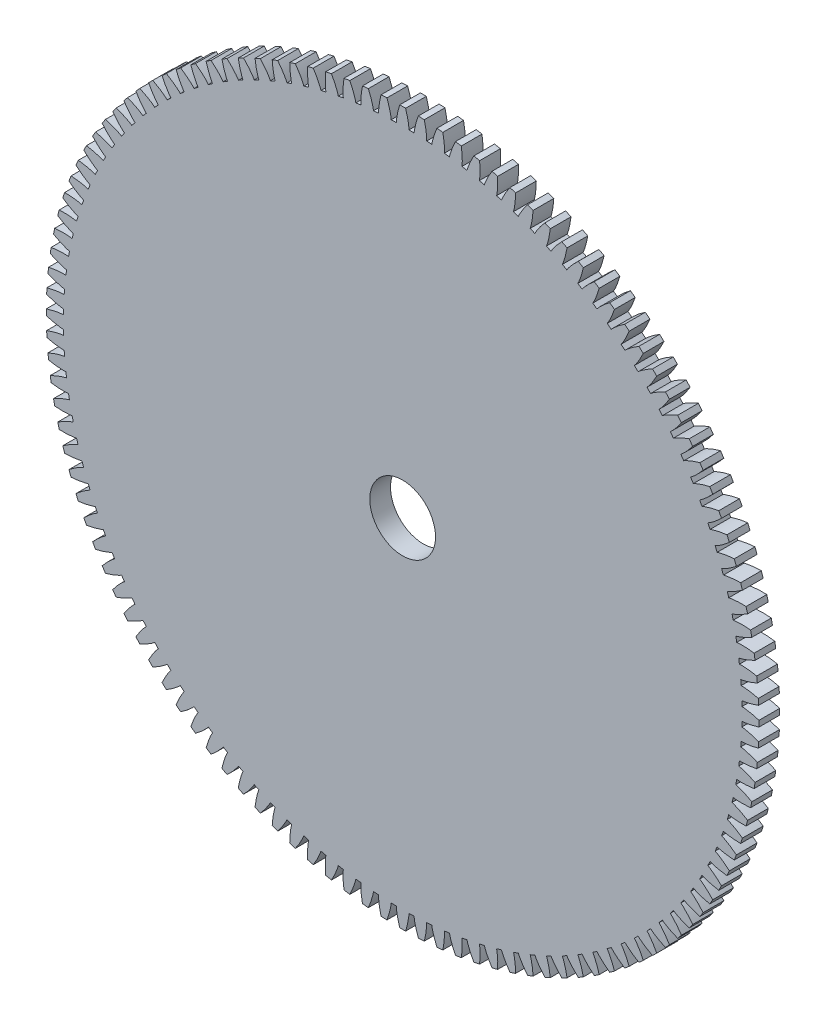
SolidWorks part; units mm, degrees
material "Brass"
ref_plane "Front Plane" through (0, 0, 0) normal (0, 0, 1) x (1, 0, 0)
ref_plane "Top Plane" through (0, 0, 0) normal (0, 1, 0) x (1, 0, 0)
ref_plane "Right Plane" through (0, 0, 0) normal (1, 0, 0) x (0, 0, -1)
sketch "Sketch1" plane through (0, 0, 0) normal (0, 0, 1) x (1, 0, 0)
  circle A0 centre (0, 0) radius 51.6467
  dimension "D1" = 103.2933
extrude "Boss-Extrude1" add sketch "Sketch1" along normal blind 3
sketch "Sketch2" plane through (0, 0, 0) normal (0, 0, 1) x (1, 0, 0)
  spline S0 degree 4 poles (49.1734, 0.9164) (49.1838, 0.9166) (49.2037, 0.9164) (49.236, 0.9157) (49.2811, 0.9138) (49.3345, 0.9109) (49.3975, 0.9065) (49.4669, 0.9007) (49.5426, 0.8933) (49.6181, 0.8849) (49.6937, 0.8757) (49.769, 0.8656) (49.8604, 0.8525) (49.9703, 0.8355) (50.099, 0.8136) (50.2454, 0.7864) (50.3952, 0.7562) (50.5429, 0.7245) (50.6927, 0.69) (50.8381, 0.655) (50.9896, 0.6161) (51.1298, 0.579) (51.2875, 0.5348) (51.415, 0.4982) (51.584, 0.4471) (51.6841, 0.416) (51.8014, 0.3786) (51.8537, 0.3614) (51.8859, 0.3509) knots 0 0 0 0 0 0.015084 0.028532 0.04661 0.064855 0.092111 0.119476 0.146842 0.174209 0.201575 0.228941 0.256307 0.307035 0.361767 0.4165 0.471232 0.525964 0.580697 0.635429 0.690161 0.744894 0.799626 0.854358 0.909091 0.954545 1 1 1 1 1 construction
  spline S1 degree 4 poles (49.1734, 0.9164) (49.1838, 0.9166) (49.2037, 0.9164) (49.236, 0.9157) (49.2811, 0.9138) (49.3345, 0.9109) (49.3975, 0.9065) (49.4669, 0.9007) (49.5426, 0.8933) (49.6181, 0.8849) (49.6937, 0.8757) (49.769, 0.8656) (49.8604, 0.8525) (49.9703, 0.8355) (50.099, 0.8136) (50.2454, 0.7864) (50.3952, 0.7562) (50.5429, 0.7245) (50.6927, 0.69) (50.8381, 0.655) (50.9896, 0.6161) (51.1298, 0.579) (51.2875, 0.5348) (51.415, 0.4982) (51.5474, 0.4582) (51.6119, 0.4383) (51.6449, 0.428) knots 0 0 0 0 0 0.015084 0.028532 0.04661 0.064855 0.092111 0.119476 0.146842 0.174209 0.201575 0.228941 0.256307 0.307035 0.361767 0.4165 0.471232 0.525964 0.580697 0.635429 0.690161 0.744894 0.799626 0.854358 0.909091 0.909091 0.909091 0.909091 0.909091
  spline S2 degree 4 poles (49.1539, 1.6583) (49.1644, 1.6588) (49.1842, 1.66) (49.2165, 1.6624) (49.2614, 1.6666) (49.3146, 1.6723) (49.3773, 1.68) (49.4463, 1.6894) (49.5214, 1.7008) (49.5965, 1.7131) (49.6714, 1.7263) (49.7461, 1.7403) (49.8367, 1.7581) (49.9455, 1.7809) (50.0729, 1.8095) (50.2177, 1.8443) (50.3657, 1.8823) (50.5116, 1.9217) (50.6594, 1.964) (50.8027, 2.0066) (50.952, 2.0533) (51.09, 2.0977) (51.2452, 2.1502) (51.3706, 2.1933) (51.5367, 2.2532) (51.635, 2.2895) (51.7503, 2.333) (51.8016, 2.3529) (51.8332, 2.3651) knots 0 0 0 0 0 0.015084 0.028532 0.04661 0.064855 0.092111 0.119476 0.146842 0.174209 0.201575 0.228941 0.256307 0.307035 0.361767 0.4165 0.471232 0.525964 0.580697 0.635429 0.690161 0.744894 0.799626 0.854358 0.909091 0.954545 1 1 1 1 1 construction
  spline S3 degree 4 poles (49.1539, 1.6583) (49.1644, 1.6588) (49.1842, 1.66) (49.2165, 1.6624) (49.2614, 1.6666) (49.3146, 1.6723) (49.3773, 1.68) (49.4463, 1.6894) (49.5214, 1.7008) (49.5965, 1.7131) (49.6714, 1.7263) (49.7461, 1.7403) (49.8367, 1.7581) (49.9455, 1.7809) (50.0729, 1.8095) (50.2177, 1.8443) (50.3657, 1.8823) (50.5116, 1.9217) (50.6594, 1.964) (50.8027, 2.0066) (50.952, 2.0533) (51.09, 2.0977) (51.2452, 2.1502) (51.3706, 2.1933) (51.5007, 2.2403) (51.5641, 2.2634) (51.5965, 2.2754) knots 0 0 0 0 0 0.015084 0.028532 0.04661 0.064855 0.092111 0.119476 0.146842 0.174209 0.201575 0.228941 0.256307 0.307035 0.361767 0.4165 0.471232 0.525964 0.580697 0.635429 0.690161 0.744894 0.799626 0.854358 0.909091 0.909091 0.909091 0.909091 0.909091
  spline S4 degree 1 poles (49.1539, 1.6583) (49.1734, 0.9164) knots 0 0 1 1 construction
  spline S5 degree 1 poles (49.1539, 1.6583) (49.1734, 0.9164) knots 0 0 1 1
  spline S6 degree 1 poles (51.6449, 0.428) (59.9979, 0.4973) knots 0 0 1 1 construction
  spline S7 degree 1 poles (51.6449, 0.428) (59.9979, 0.4973) knots 0 0 1 1
  spline S8 degree 4 poles (59.9993, 0.2811) (59.9993, 0.2966) (59.9991, 0.3264) (59.9989, 0.3667) (59.9981, 0.4759) (59.9977, 0.5237) (59.9964, 0.6646) (59.9954, 0.7445) (59.9939, 0.8601) (59.9924, 0.9543) (59.9907, 1.0614) (59.9888, 1.1607) (59.9867, 1.2646) (59.9845, 1.3658) (59.9821, 1.4686) (59.9795, 1.5706) (59.9767, 1.6727) (59.9738, 1.7754) (59.9707, 1.8766) (59.9673, 1.9805) (59.964, 2.0797) (59.9601, 2.1868) (59.9567, 2.2809) (59.9521, 2.3964) (59.949, 2.4763) (59.9429, 2.6171) (59.9408, 2.6648) (59.9359, 2.7739) (59.934, 2.8142) (59.9326, 2.844) (59.9318, 2.8594) knots 0 0 0 0 0 0.020959 0.041918 0.083333 0.123016 0.162698 0.202381 0.242063 0.281746 0.321429 0.361111 0.400794 0.440476 0.480159 0.519841 0.559524 0.599206 0.638889 0.678571 0.718254 0.757937 0.797619 0.837302 0.876984 0.916667 0.958082 0.979041 1 1 1 1 1 construction
  spline S9 degree 4 poles (59.9979, 0.4973) (59.9978, 0.5186) (59.9974, 0.5601) (59.9964, 0.6646) (59.9954, 0.7445) (59.9939, 0.8601) (59.9924, 0.9543) (59.9907, 1.0614) (59.9888, 1.1607) (59.9867, 1.2646) (59.9845, 1.3658) (59.9821, 1.4686) (59.9795, 1.5706) (59.9767, 1.6727) (59.9738, 1.7754) (59.9707, 1.8766) (59.9673, 1.9805) (59.964, 2.0797) (59.9601, 2.1868) (59.9567, 2.2809) (59.9521, 2.3964) (59.949, 2.4763) (59.9445, 2.5807) (59.9427, 2.6222) (59.9417, 2.6435) knots 0.083333 0.083333 0.083333 0.083333 0.083333 0.123016 0.162698 0.202381 0.242063 0.281746 0.321429 0.361111 0.400794 0.440476 0.480159 0.519841 0.559524 0.599206 0.638889 0.678571 0.718254 0.757937 0.797619 0.837302 0.876984 0.916667 0.916667 0.916667 0.916667 0.916667
  spline S10 degree 1 poles (59.9417, 2.6435) (51.5965, 2.2754) knots 0 0 1 1 construction
  spline S11 degree 1 poles (59.9417, 2.6435) (51.5965, 2.2754) knots 0 0 1 1
extrude "Cut-Extrude2" cut sketch "Sketch2" against normal blind 4 and the other way blind 4
ref_axis "Axis1" through (0, 0, -0.15) along (0, 0, 1)
pattern_circular "CirPattern1" count 120 over 360 about axis through (0, 0, -0.15) along (0, 0, 1) of "Cut-Extrude2"
sketch "Sketch3" plane through (0, 0, 0) normal (0, 0, 1) x (1, 0, 0)
  circle A0 centre (0, 0) radius 4.7625
  dimension "D1" = 9.525
extrude "Cut-Extrude4" cut sketch "Sketch3" against normal blind 5 and the other way blind 5
